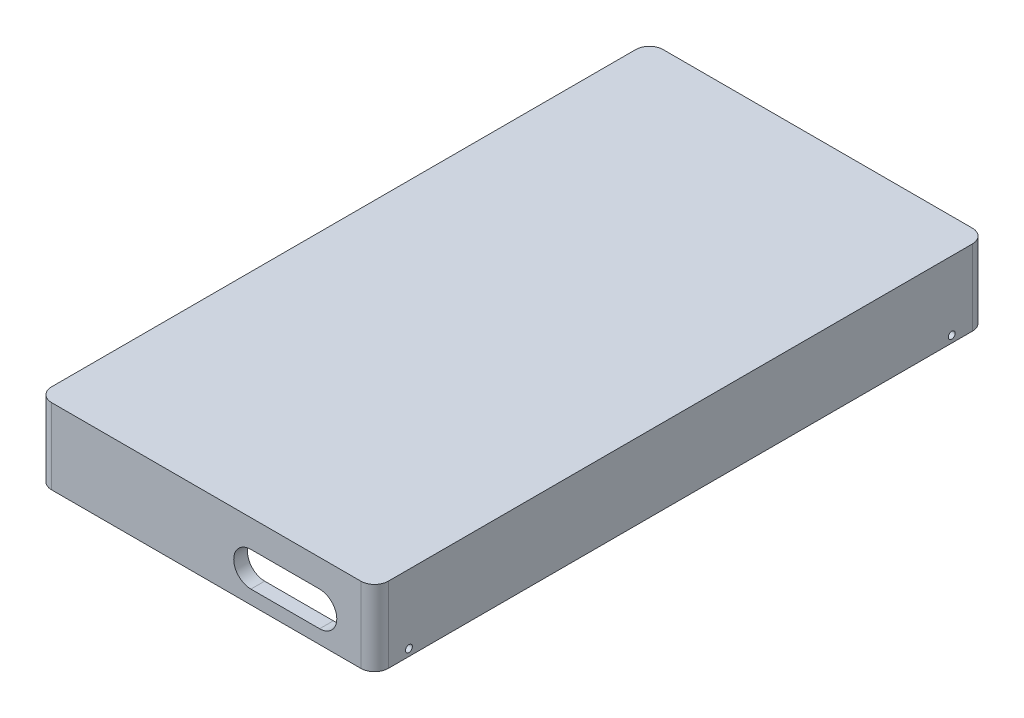
SolidWorks part; units mm, degrees
ref_plane "Front Plane" through (0, 0, 0) normal (0, 0, 1) x (1, 0, 0)
ref_plane "Top Plane" through (0, 0, 0) normal (0, 1, 0) x (1, 0, 0)
ref_plane "Right Plane" through (0, 0, 0) normal (1, 0, 0) x (0, 0, -1)
sketch "Sketch1" plane through (0, 0, 0) normal (0, 1, 0) x (1, 0, 0)
  line L1 (0, 0) -> (57.15, 0)
  line L2 (0, 0) -> (0, 107.95)
  line L3 (0, 107.95) -> (57.15, 107.95)
  line L4 (57.15, 0) -> (57.15, 107.95)
  dimension "D1" = 107.95
  dimension "D2" = 57.15
extrude "Boss-Extrude1" add sketch "Sketch1" along normal blind 2.54
sketch "Sketch2" plane through (0, 2.54, 0) normal (0, 1, 0) x (1, 0, 0)
  line L0 (0, 53.975) -> (57.15, 53.975) construction
  line L1 (0, 107.95) -> (0, 0) construction
  line L2 (57.15, 0) -> (57.15, 107.95) construction
  line L3 (28.575, 107.95) -> (28.575, 0) construction
  line L4 (57.15, 107.95) -> (0, 107.95) construction
  line L5 (0, 0) -> (57.15, 0) construction
  line L7 (-2.54, -2.54) -> (59.69, -2.54)
  line L8 (-2.54, -2.54) -> (-2.54, 110.49)
  line L9 (-2.54, 110.49) -> (59.69, 110.49)
  line L10 (59.69, -2.54) -> (59.69, 110.49)
  line L11 (-2.54, -2.54) -> (59.69, 110.49) construction
  line L12 (-2.54, 110.49) -> (59.69, -2.54) construction
  line L13 (0, 0) -> (57.15, 0)
  line L14 (0, 0) -> (0, 107.95)
  line L15 (0, 107.95) -> (57.15, 107.95)
  line L16 (57.15, 0) -> (57.15, 107.95)
  line L17 (0, 0) -> (57.15, 107.95) construction
  line L18 (0, 107.95) -> (57.15, 0) construction
  point P12 (28.575, 53.975)
  point P17 (28.575, 53.975)
  dimension "D1" = 2.54
  dimension "D2" = 2.54
extrude "Boss-Extrude3" add sketch "Sketch2" against normal blind 13.97
sketch "Sketch3" plane through (0, 0, 2.54) normal (0, 0, 1) x (1, 0, 0)
  line L0 (-2.54, -5.715) -> (59.69, -5.715) construction
  line L1 (-2.54, -11.43) -> (-2.54, 2.54) construction
  line L3 (28.575, 2.54) -> (28.575, -11.43) construction
  line L4 (-2.54, 2.54) -> (59.69, 2.54) construction
  line L5 (-2.54, -11.43) -> (59.69, -11.43) construction
  line L6 (36.83, -5.715) -> (49.53, -5.715) construction
  line L7 (36.83, -2.54) -> (49.53, -2.54)
  line L8 (36.83, -8.89) -> (49.53, -8.89)
  arc A0 (36.83, -2.54) -> (36.83, -8.89) centre (36.83, -5.715) ccw
  arc A1 (49.53, -8.89) -> (49.53, -2.54) centre (49.53, -5.715) ccw
  point P4 (0, 0)
  point P14 (43.18, -5.715)
  dimension "D1" = 39.37
  dimension "D2" = 12.7
  dimension "D3" = 6.35
  dimension "D4" = 8.255
extrude "Cut-Extrude1" cut sketch "Sketch3" against normal blind 10.16
fillet "Fillet1" radius 2.54 4 edges at (-2.54, -4.445, -110.49) (59.69, -4.445, -110.49) (59.69, -4.445, 2.54) (-2.54, -4.445, 2.54)
sketch "Sketch4" plane through (-2.54, 0, 0) normal (-1, 0, 0) x (0, 0, 1)
  line L0 (-107.95, -10.16) -> (0, -10.16) construction
  line L1 (-107.95, 2.54) -> (-107.95, -11.43) construction
  line L2 (0, -11.43) -> (0, 2.54) construction
  line L3 (-107.95, -11.43) -> (0, -11.43) construction
  line L4 (-53.975, 2.54) -> (-53.975, -11.43) construction
  line L5 (-107.95, 2.54) -> (0, 2.54) construction
  circle A0 centre (-104.14, -10.16) radius 0.635
  circle A1 centre (-3.81, -10.16) radius 0.635
  dimension "D2" = 1.27
  dimension "D3" = 3.81
  dimension "D1" = 1.27
extrude "Cut-Extrude2" cut sketch "Sketch4" against normal through all
